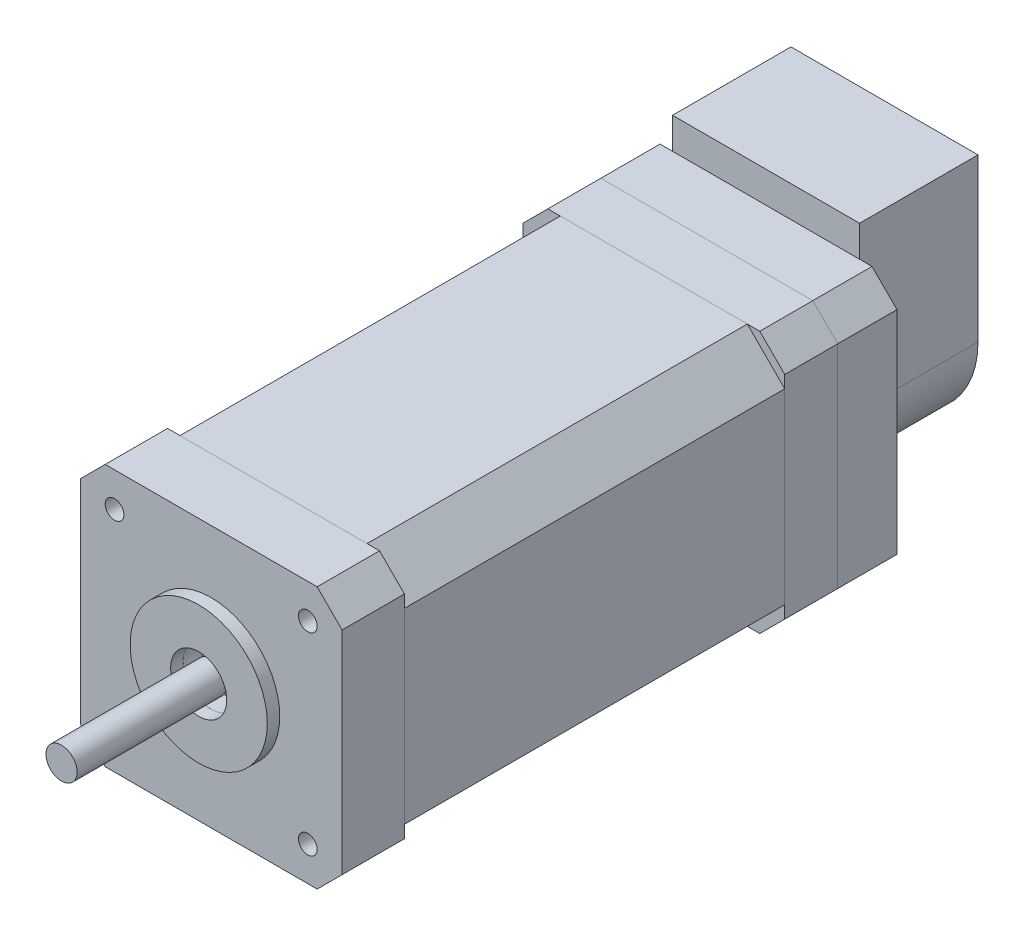
SolidWorks part; units mm, degrees
material "AISI 304"
ref_plane "前基準面" through (0, 0, 0) normal (0, 0, 1) x (1, 0, 0)
ref_plane "上基準面" through (0, 0, 0) normal (0, 1, 0) x (1, 0, 0)
ref_plane "右基準面" through (0, 0, 0) normal (1, 0, 0) x (0, 0, -1)
sketch "草圖1" plane through (0, 0, 0) normal (0, 0, 1) x (1, 0, 0)
  line L1 (-21, -21) -> (21, -21)
  line L2 (-21, -21) -> (-21, 21)
  line L3 (-21, 21) -> (21, 21)
  line L4 (21, -21) -> (21, 21)
  line L5 (-21, -21) -> (21, 21) construction
  line L6 (-21, 21) -> (21, -21) construction
  point P0 (0, 0)
  dimension "D1" = 42
  dimension "D2" = 42
extrude "填料-伸長1" add sketch "草圖1" along normal mid plane 61
chamfer "導角1" distance 6 angle 45 4 edges at (21, -21, 0) (-21, -21, 0) (-21, 21, 0) (21, 21, 0)
sketch "草圖15" plane through (0, 0, 30.5) normal (0, 0, 1) x (1, 0, 0)
  line L0 (15, 21) -> (-15, 21) construction
  line L1 (-21, -21) -> (21, -21)
  line L2 (-21, -21) -> (-21, 21)
  line L3 (-21, 21) -> (21, 21)
  line L4 (21, -21) -> (21, 21)
  line L5 (-21, -21) -> (21, 21) construction
  line L6 (-21, 21) -> (21, -21) construction
  line L7 (21, -15) -> (21, 15) construction
  point P0 (0, 0)
extrude "填料-伸長11" add sketch "草圖15" along normal blind 10 separate body
sketch "草圖16" plane through (0, 0, -30.5) normal (0, 0, -1) x (-1, 0, 0)
  line L1 (-21, -21) -> (21, -21)
  line L2 (-21, -21) -> (-21, 21)
  line L3 (-21, 21) -> (21, 21)
  line L4 (21, -21) -> (21, 21)
  line L5 (-21, -21) -> (21, 21) construction
  line L6 (-21, 21) -> (21, -21) construction
  line L8 (-15, 21) -> (15, 21) construction
  line L9 (21, 15) -> (21, -15) construction
  point P0 (0, 0)
extrude "填料-伸長12" add sketch "草圖16" along normal blind 8.5 separate body
sketch "草圖17" plane through (0, 0, -39) normal (0, 0, 1) x (1, 0, 0)
  line L0 (-21, 21) -> (21, 21) construction
  line L1 (-21, -21) -> (21, -21)
  line L2 (-21, -21) -> (-21, 21)
  line L3 (-21, 21) -> (21, 21)
  line L4 (21, -21) -> (21, 21)
  line L5 (-21, -21) -> (21, 21) construction
  line L6 (-21, 21) -> (21, -21) construction
  line L7 (21, 21) -> (21, -21) construction
  point P0 (0, 0)
extrude "填料-伸長13" add sketch "草圖17" against normal blind 9.5 separate body
chamfer "導角2" distance 4 angle 45 4 edges at (-21, -21, 35.5) (21, -21, 35.5) (21, 21, 35.5) (-21, 21, 35.5)
chamfer "導角3" distance 4 angle 45 4 edges at (-21, -21, -34.75) (21, -21, -34.75) (-21, 21, -34.75) (21, 21, -34.75)
chamfer "導角4" distance 4 angle 45 4 edges at (21, 21, -43.75) (-21, 21, -43.75) (-21, -21, -43.75) (21, -21, -43.75)
sketch "草圖2" plane through (0, 0, 40.5) normal (0, 0, 1) x (1, 0, 0)
  circle A0 centre (0, 0) radius 11
  dimension "D1" = 22
extrude "填料-伸長2" add sketch "草圖2" along normal blind 2
sketch "草圖3" plane through (0, 0, 42.5) normal (0, 0, 1) x (1, 0, 0)
  circle A0 centre (0, 0) radius 4.5
  dimension "D1" = 9
extrude "除料-伸長1" cut sketch "草圖3" along direction (0, 0, -1) on the side against the normal blind 5
sketch "草圖6" plane through (0, 0, 40.5) normal (0, 0, 1) x (1, 0, 0)
  circle A0 centre (0, 0) radius 2.5
  dimension "D1" = 5
extrude "填料-伸長9" add sketch "草圖6" along direction (0, 0, 1) on the side of the normal offset from surface (24 mm away) 22 separate body up to face at (4.5, 0, 42.5) offset beyond the face yes
sketch "草圖9" plane through (0, 0, -48.5) normal (0, 0, -1) x (-1, 0, 0)
  line L0 (-15, 0) -> (-15, 26)
  line L1 (-15, 26) -> (15, 26)
  line L2 (15, 26) -> (15, 0)
  arc A0 (15, 0) -> (-15, 0) centre (0, 0) cw
  point P6 (0, -15)
  dimension "D1" = 15
  dimension "D2" = 41
extrude "填料-伸長10" add sketch "草圖9" along normal blind 19 separate body
sketch "草圖8" plane through (0, 0, 40.5) normal (0, 0, 1) x (1, 0, 0)
  line L0 (0, 0) -> (0, 15.5) construction
  line L1 (0, 15.5) -> (-15.5, 15.5) construction
  circle A0 centre (-15.5, 15.5) radius 1.5
  dimension "D3" = 3
  dimension "D1" = 15.5
  dimension "D2" = 15.5
extrude "除料-伸長3" cut sketch "草圖8" against normal blind 4.5
sketch "草圖11" plane through (0, 0, 64.5) normal (0, 0, 1) x (1, 0, 0)
  line L0 (-2, 1.5) -> (2, 1.5)
  circle A0 centre (0, 0) radius 2.5 construction
  arc A1 (2, 1.5) -> (-2, 1.5) centre (0, 0) ccw
  point P5 (0, 1.5)
  point P6 (0, 2.5)
  dimension "D1" = 1
extrude "除料-伸長4" [suppressed] cut sketch "草圖11" against normal blind 18
pattern_circular "環狀複製排列1" count 4 over 360 about axis through (0, 0, 40.5) along (0, 0, 1) of "除料-伸長3"
